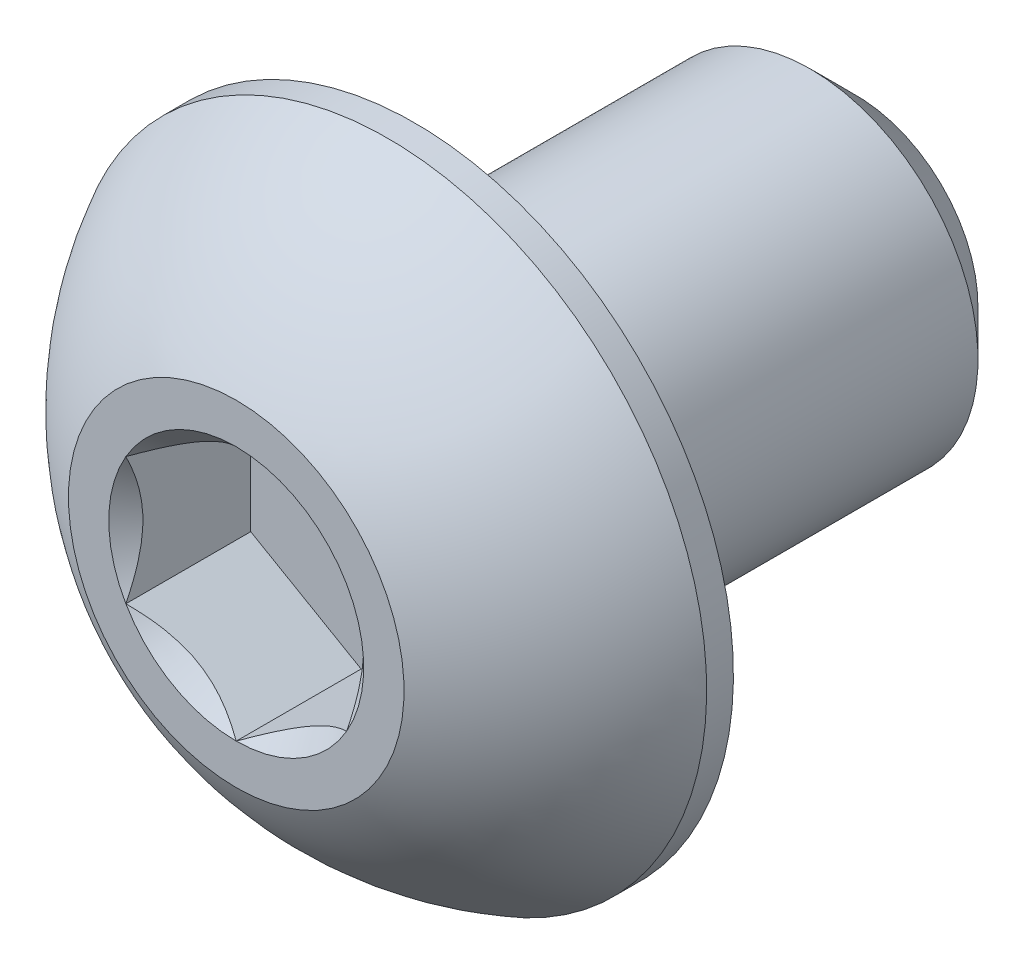
SolidWorks part; units mm, degrees
material "Alloy Steel"
ref_plane "Front" through (0, 0, 0) normal (0, 0, 1) x (1, 0, 0)
ref_plane "Top" through (0, 0, 0) normal (0, 1, 0) x (1, 0, 0)
ref_plane "Right" through (0, 0, 0) normal (1, 0, 0) x (0, 0, -1)
sketch "Sketch1" plane through (0, 0, 0) normal (1, 0, 0) x (0, 0, -1)
  line L2 (-1.8923, 2.413) -> (4.4577, 2.413) construction
  line L3 (4.4577, 2.413) -> (4.4577, 0) construction
  line L4 (4.4577, 0) -> (-4.4577, 0) construction
  line L6 (-2.2771, 4.5847) -> (-1.8923, 4.5847) construction
  line L7 (4.4577, 2.413) -> (4.4577, -2.413) construction
  line L8 (-4.4577, 0) -> (-1.8923, 0) construction
  line L9 (-1.8923, 4.5847) -> (-1.8923, -4.5847) construction
  line L11 (-1.8923, 2.413) -> (-1.8923, 0) construction
  line L13 (-4.4577, 1.5875) -> (-4.4577, -1.5875) construction
  line L14 (-4.4577, 1.5875) -> (-4.4577, 2.413) construction
  arc A3 (-4.4577, 2.413) -> (-2.2771, 4.5847) centre (0.1172, 0) cw construction
  point P10 (2.8702, -2.413)
  point P16 (-0.3048, 0)
  point P19 (2.8702, 0)
  point P20 (0, 0)
  dimension "Thread OD" = 4.826
  dimension "D1" = 0.3848
  dimension "Head Height" = 2.5654
  dimension "Head Diameter" = 9.1694
  dimension "D2" = 1.5875
  dimension "D3" = 1.5875
  dimension "D4" = 1.5875
sketch "Sketch11" plane through (0, 0, 0) normal (1, 0, 0) x (0, 0, -1)
  line L1 (-1.8923, 0) -> (4.4577, 0)
  line L4 (-1.8923, 2.413) -> (4.4577, 2.413) construction
  line L5 (4.4577, 2.413) -> (4.4577, 0) construction
  line L8 (-1.8923, 2.413) -> (4.4577, 2.413)
  line L9 (4.4577, 2.413) -> (4.4577, 0)
  line L10 (-1.8923, 2.413) -> (-1.8923, 0)
revolve "Revolve1" add sketch "Sketch11" angle 360 about L1
chamfer "Chamfer1" distance 0.6615 angle 45 1 edges at (0, -2.413, -4.4577)
sketch "Sketch7" plane through (0, 0, 0) normal (1, 0, 0) x (0, 0, -1)
  line L6 (-2.2771, 4.5847) -> (-1.8923, 4.5847) construction
  line L8 (-4.4577, 0) -> (-1.8923, 0) construction
  line L11 (-1.8923, 4.5847) -> (-1.8923, -4.5847) construction
  line L12 (-2.2771, 4.5847) -> (-1.8923, 4.5847)
  line L13 (-4.4577, 0) -> (-1.8923, 0)
  line L14 (-4.4577, 1.5875) -> (-4.4577, -1.5875) construction
  line L15 (-1.8923, 4.5847) -> (-1.8923, 0)
  line L16 (-4.4577, 2.413) -> (-4.4577, 0)
  arc A2 (-2.2771, 4.5847) -> (-4.4577, 2.413) centre (0.1172, 0) ccw construction
  arc A3 (-2.2771, 4.5847) -> (-4.4577, 2.413) centre (0.1172, 0) ccw
revolve "Revolve2" add sketch "Sketch7" angle 360 mid plane about L13
sketch "Sketch5" plane through (0, 0, 4.4577) normal (0, 0, 1) x (1, 0, 0)
  line L1 (1.5875, -0.9165) -> (1.5875, 0.9165)
  line L2 (1.5875, 0.9165) -> (0, 1.8331)
  line L3 (0, 1.8331) -> (-1.5875, 0.9165)
  line L4 (-1.5875, 0.9165) -> (-1.5875, -0.9165)
  line L5 (-1.5875, -0.9165) -> (0, -1.8331)
  line L6 (0, -1.8331) -> (1.5875, -0.9165)
  circle A0 centre (0, 0) radius 1.5875 construction
extrude "Cut-Extrude2" cut sketch "Sketch5" against normal blind 1.7958
sketch "Sketch6" plane through (0, 0, 4.4577) normal (0, 0, 1) x (1, 0, 0)
  circle A0 centre (0, 0) radius 1.8331
extrude "Cut-Extrude3" cut sketch "Sketch6" against normal blind 1.7958 draft 45
sketch "Sketch3" [suppressed] plane through (0, 0, -4.4577) normal (0, 0, -1) x (-1, 0, 0)
  circle A0 centre (0, 0) radius 2.413
curve "Helix/Spiral1" [suppressed] pitch 1.0583 height 7.4083 turns 7
sketch "Sketch2" [suppressed] plane through (0, 0, 0) normal (1, 0, 0) x (0, 0, -1)
  line L0 (4.3916, 2.5276) -> (5.4499, 2.5276) construction
  line L1 (5.4499, 2.5276) -> (4.9207, 1.611) construction
  line L2 (4.9207, 1.611) -> (4.3916, 2.5276) construction
  line L3 (4.9207, 1.611) -> (4.9207, 1.7256) construction
  line L4 (4.9207, 1.7256) -> (4.9207, 2.413) construction
  line L5 (4.9207, 2.413) -> (4.9207, 2.5276) construction
  line L6 (4.9869, 1.7256) -> (4.8546, 1.7256) construction
  line L7 (5.3837, 2.413) -> (4.4577, 2.413) construction
  line L8 (5.4168, 2.4703) -> (4.4246, 2.4703) construction
  line L9 (4.4246, 2.4703) -> (5.4168, 2.4703)
  line L10 (5.4168, 2.4703) -> (4.9869, 1.7256)
  line L11 (4.9869, 1.7256) -> (4.8546, 1.7256)
  line L12 (4.8546, 1.7256) -> (4.4246, 2.4703)
  line L13 (4.4577, 2.413) -> (-1.8923, 2.413) construction
  line L14 (4.4577, -2.413) -> (4.4577, 2.413)
  line L15 (4.4577, -2.413) -> (4.4577, 2.413) construction
  line L16 (-1.8923, -4.5847) -> (-1.8923, 4.5847) construction
  point P10 (4.9207, 1.7256)
  point P11 (4.9207, 2.413)
  point P16 (4.9207, 2.4703)
  dimension "D1" = 1.0583
  dimension "D2" = 0.1323
sweep "Cut-Sweep1" [suppressed] cut profiles "Sketch2" path "Helix/Spiral1"
combine bodies "Combine1" [suppressed] operation type add bodies to combine 120 121
equation "\"D3@Helix/Spiral1\" = \"Length@Sketch1\" + \"D4@Helix/Spiral1\""
equation "\"D1@Chamfer1\"=\"D4@Helix/Spiral1\" * .625"
equation "\"D1@Cut-Extrude2\" = \"Head Height@Sketch1\" * .7"
equation "\"D1@Sketch1\" = \"Head Height@Sketch1\" * .15"
equation "\"D1@Cut-Extrude3\" = \"D1@Cut-Extrude2\""
equation "\"D2@Sketch1\"=\"D4@Helix/Spiral1\"*1.5"
equation "\"D3@Sketch1\" = \"Length@Sketch1\" / 4"
equation "\"D4@Sketch1\"=\"D3@Sketch1\""
equation "\"D1@Sketch2\"=\"D4@Helix/Spiral1\""
equation "\"D2@Sketch2\"=\"D1@Sketch2\"/8"
